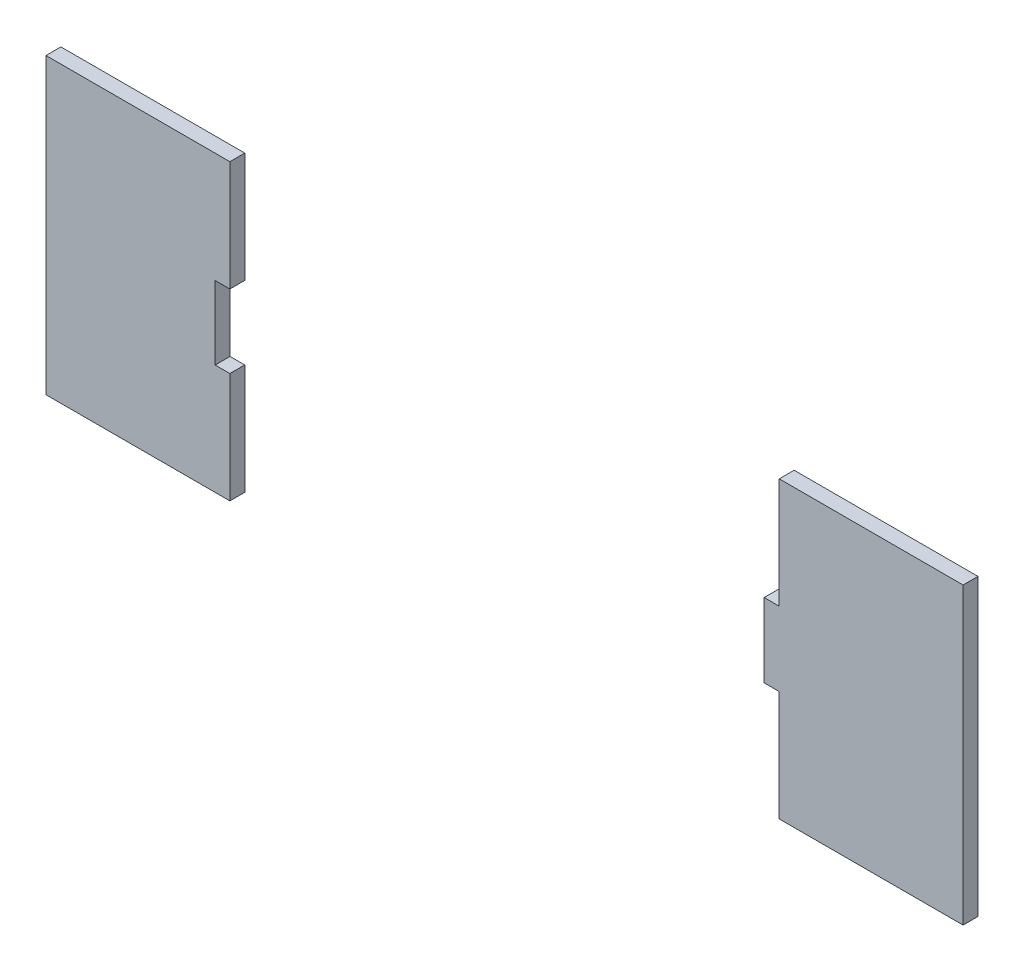
SolidWorks part; units mm, degrees
ref_plane "Piano frontale" through (0, 0, 0) normal (0, 0, 1) x (1, 0, 0)
ref_plane "Piano superiore" through (0, 0, 0) normal (0, 1, 0) x (1, 0, 0)
ref_plane "Piano destro" through (0, 0, 0) normal (1, 0, 0) x (0, 0, -1)
sketch "Schizzo1" plane through (0, 0, 0) normal (0, 0, 1) x (1, 0, 0)
  line L0 (-1.6733, -33.7217) -> (-1.6733, -63.7217)
  line L1 (-51.6733, 16.1783) -> (-1.6733, 16.1783)
  line L2 (-51.6733, 16.1783) -> (-51.6733, -63.7217)
  line L3 (-51.6733, -63.7217) -> (-1.6733, -63.7217)
  line L4 (-1.6733, 16.1783) -> (-1.6733, -13.8217)
  line L5 (-1.6733, -13.8217) -> (-5.6733, -13.8217)
  line L6 (147.7249, -33.9217) -> (147.7249, -63.9217)
  line L7 (-1.6733, -33.7217) -> (-5.6733, -33.7217)
  line L8 (-5.6733, -13.8217) -> (-5.6733, -33.7217)
  line L9 (147.7249, 16.1783) -> (197.7249, 16.1783)
  line L10 (147.7249, 16.1783) -> (147.7249, -13.8217)
  line L11 (147.7249, -63.9217) -> (197.7249, -63.9217)
  line L12 (197.7249, 16.1783) -> (197.7249, -63.9217)
  line L13 (147.7249, -13.8217) -> (143.6249, -13.8217)
  line L15 (147.7249, -33.9217) -> (143.6249, -33.9217)
  line L16 (143.6249, -13.8217) -> (143.6249, -33.9217)
  dimension "D1" = 50
  dimension "d" = 30
  dimension "D2" = 30
  dimension "D3" = 50
  dimension "D7" = 30
  dimension "D8" = 30
  dimension "D6" = 4
  dimension "D5" = 4.1
  dimension "D4" = 19.9
  dimension "D9" = 20.1
extrude "Estrusione-Estrusione1" add sketch "Schizzo1" along normal blind 4.05 contours L1 L4 L5 L8 L7 L0 L3 L2
extrude "Estrusione-Estrusione2" add sketch "Schizzo1<3>" along normal blind 4.05 separate body contours L9 L12 L11 L6 L15 L16 L13 L10
sketch "Schizzo1<3>" plane through (0, 0, 0) normal (0, 0, 1) x (1, 0, 0) same geometry as "Schizzo1"
equation "\"m\"= 4.05mm'material thickness"
equation "\"k\"= 0.05mm'material kerf"
equation "\"tm\" = \"m\" + \"k\"'total thickness male"
equation "\"tf\"= \"m\" - \"k\"'total thickness female"
equation "\"l\"= 50mm'lateral lenght"
equation "\"jh\"= 20mm'arbitrary joint height"
equation "\"d\"= 30'joint-edge distance"
equation "\"D1@Schizzo1\"=\"l\""
equation "\"d@Schizzo1\" = \"d\""
equation "\"D2@Schizzo1\"=\"d\""
equation "\"D7@Schizzo1\"=\"d\""
equation "\"D8@Schizzo1\"=\"d\""
equation "\"jm\" = \"jh\" + 2 * \"k\"'male joint height"
equation "\"jf\" = \"jh\" - 2 * \"k\"'female joint height"
equation "\"D4@Schizzo1\"=\"jf\""
equation "\"D9@Schizzo1\"=\"jm\""
equation "\"D5@Schizzo1\"=\"tm\""
equation "\"D6@Schizzo1\"=\"tf\""
